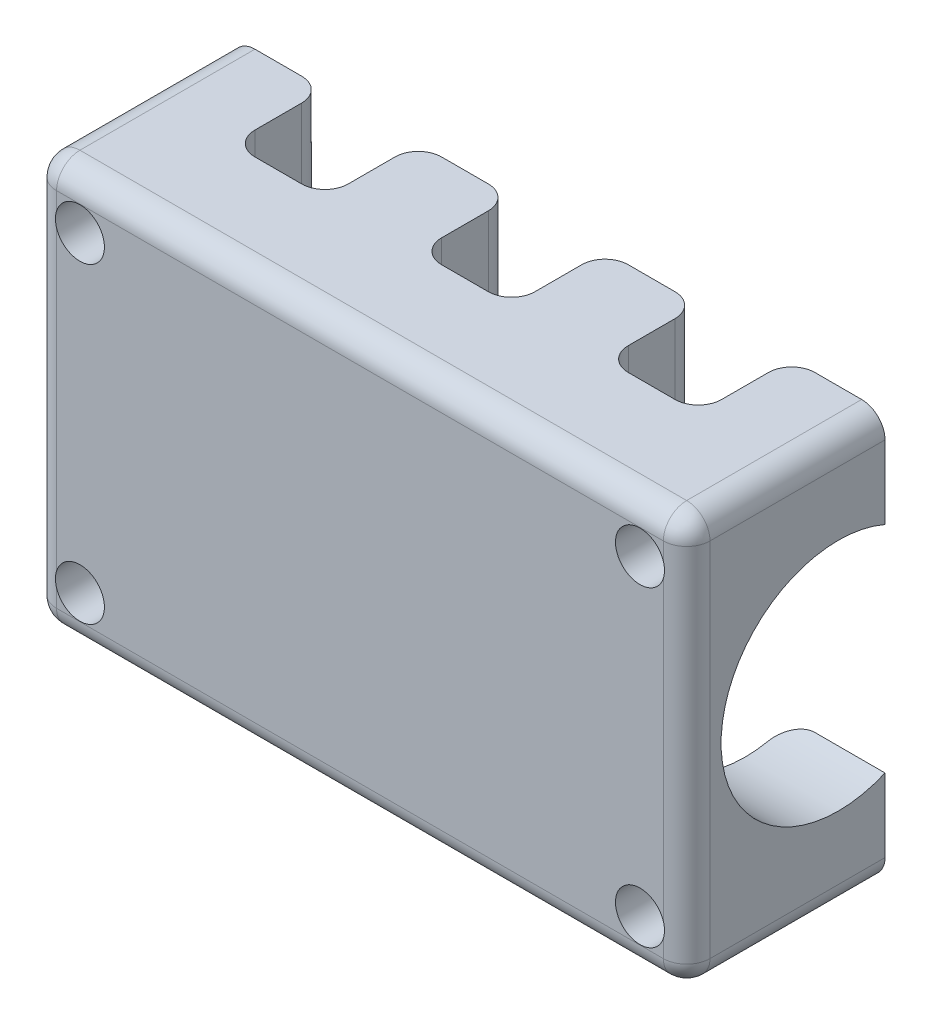
SolidWorks part; units mm, degrees
ref_plane "前视基准面" through (0, 0, 0) normal (0, 0, 1) x (1, 0, 0)
ref_plane "上视基准面" through (0, 0, 0) normal (0, 1, 0) x (1, 0, 0)
ref_plane "右视基准面" through (0, 0, 0) normal (1, 0, 0) x (0, 0, -1)
other "Configuration Table"
sketch "草图1" plane through (0, 0, 0) normal (0, 0, 1) x (1, 0, 0)
  line L1 (0, 0) -> (56, 0)
  line L2 (0, 0) -> (0, -35)
  line L3 (0, -35) -> (56, -35)
  line L4 (56, 0) -> (56, -35)
  dimension "D1" = 56
  dimension "D2" = 35
extrude "凸台-拉伸1" add sketch "草图1" along normal blind 26 contours L2 L1 L4 L3
sketch "草图2" plane through (0, 0, 0) normal (-1, 0, 0) x (0, 0, 1)
  line L0 (13, 0) -> (13, -35) construction
  line L1 (26, 0) -> (0, 0) construction
  line L2 (26, -35) -> (0, -35) construction
  line L3 (0, -17.5) -> (26, -17.5) construction
  line L4 (0, 0) -> (0, -35) construction
  line L5 (26, 0) -> (26, -35) construction
  circle A0 centre (13, -17.5) radius 10.05
  dimension "D1" = 20.1
extrude "切除-拉伸1" cut sketch "草图2" against normal blind 63
sketch "草图3" plane through (0, 0, 0) normal (0, 1, 0) x (1, 0, 0)
  line L0 (0, -13) -> (56, -13) construction
  line L3 (0, -26) -> (0, 0) construction
  line L4 (28, 0) -> (28, -26) construction
  line L5 (0, 0) -> (56, 0) construction
  line L6 (0, -26) -> (56, -26) construction
  line L15 (56, -26) -> (56, 0) construction
  line L16 (0, -9) -> (8, -9)
  line L17 (8, -9) -> (8, -17)
  line L18 (8, -17) -> (16, -17)
  line L19 (16, -17) -> (16, -9)
  line L20 (56, 0) -> (0, 0)
  line L21 (0, 0) -> (0, -26)
  line L22 (0, -26) -> (56, -26)
  line L23 (56, -26) -> (56, 0)
  line L24 (56, 0) -> (0, 0)
  line L25 (0, 0) -> (0, -26)
  line L26 (0, -26) -> (56, -26)
  line L27 (56, -26) -> (56, 0)
  line L28 (16, -9) -> (24, -9)
  line L29 (24, -9) -> (24, -17)
  line L30 (24, -17) -> (32, -17)
  line L31 (32, -17) -> (32, -9)
  line L32 (32, -9) -> (40, -9)
  line L33 (40, -9) -> (40, -17)
  line L34 (40, -17) -> (48, -17)
  line L35 (48, -17) -> (48, -9)
  line L36 (48, -9) -> (56, -9)
  line M16 (56, 0) -> (0, 0)
  line M17 (0, 0) -> (0, -26)
  dimension "D1" = 0
  dimension "D2" = 9
  dimension "D3" = 8
  dimension "D4" = 8
  dimension "D5" = 8
extrude "切除-拉伸4" cut sketch "草图3" against normal blind 41 contours L35 L36 L27 L16 L17 L18 L19 L28 L29 L30 L31 L32 L33 L34 M16 M17 region at (28, 0, 6.8448)
sketch "草图6" plane through (0, 0, 26) normal (0, 0, 1) x (1, 0, 0)
  line L0 (48, -8.2803) -> (48, 0) construction
  line L1 (48, 0) -> (56, 0) construction
  line L2 (56, 0) -> (56, -8.2803) construction
  line L3 (56, -8.2803) -> (48, -8.2803) construction
  line L4 (0, -8.2803) -> (0, 0) construction
  line L5 (0, 0) -> (8, 0) construction
  line L6 (8, 0) -> (8, -8.2803) construction
  line L7 (8, -8.2803) -> (0, -8.2803) construction
  line L8 (48, -8.2803) -> (48, 0)
  line L9 (48, 0) -> (56, 0)
  line L10 (56, 0) -> (56, -8.2803)
  line L11 (56, -8.2803) -> (48, -8.2803)
  line L12 (0, -8.2803) -> (0, 0)
  line L13 (0, 0) -> (8, 0)
  line L14 (8, 0) -> (8, -8.2803)
  line L15 (8, -8.2803) -> (0, -8.2803)
  line L16 (0, -17.5) -> (56, -17.5) construction
  line L17 (0, 0) -> (0, -35) construction
  line L18 (56, 0) -> (56, -35) construction
  line L19 (0, -4.1402) -> (56, -4.1402) construction
  line L20 (4, 0) -> (4, -8.2803) construction
  line L21 (52, 0) -> (52, -8.2803) construction
  circle A0 centre (4, -4.1402) radius 2.1
  circle A1 centre (52, -4.1402) radius 2.1
  circle A2 centre (52, -30.8598) radius 2.1
  circle A3 centre (4, -30.8598) radius 2.1
  dimension "D1" = 4.2
extrude "切除-拉伸5" cut sketch "草图6" against normal blind 41 contours A0 | A1 | A2 | A3
fillet "圆角2" radius 2 24 edges at (8, -30.8598, 9) (8, -30.8598, 17) (16, -30.8598, 17) (16, -30.8598, 9) (24, -30.8598, 9) (24, -30.8598, 17) (32, -30.8598, 17) (32, -30.8598, 9) (40, -30.8598, 9) (40, -30.8598, 17) (48, -30.8598, 17) (48, -30.8598, 9) (48, -4.1402, 9) (48, -4.1402, 17) (40, -4.1402, 17) (40, -4.1402, 9) (32, -4.1402, 9) (32, -4.1402, 17) (24, -4.1402, 17) (24, -4.1402, 9) (16, -4.1402, 9) (16, -4.1402, 17) (8, -4.1402, 17) (8, -4.1402, 9)
sketch "草图7" plane through (0, 0, 26) normal (0, 0, 1) x (1, 0, 0)
  line L0 (28, 0) -> (28, -35) construction
  line L1 (7, 0) -> (7, -35) construction
  line L2 (49, 0) -> (49, -35) construction
  line L3 (7, -25.5) -> (49, -25.5)
  line L4 (0, -35) -> (56, -35)
  line L5 (56, -35) -> (56, 0)
  line L6 (56, 0) -> (0, 0)
  line L7 (0, 0) -> (0, -35)
  line L8 (0, -35) -> (56, -35)
  line L9 (56, -35) -> (56, 0)
  line L10 (56, 0) -> (0, 0)
  line L11 (0, 0) -> (0, -35)
  line L12 (7, -25.5) -> (7, -28.5)
  line L13 (7, -28.5) -> (49, -28.5)
  line L14 (49, -28.5) -> (49, -25.5)
  dimension "D2" = 42
  dimension "D3" = 25.5
  dimension "D4" = 3
  dimension "D1" = 0
sketch "草图8" plane through (0, 0, 26) normal (0, 0, 1) x (1, 0, 0)
  line L0 (28, 0) -> (28, -35) construction
  line L1 (49, 0) -> (49, -35)
  line L2 (7, 0) -> (7, -35)
  line L3 (49, -9) -> (53, -9)
  line L4 (0, -35) -> (56, -35)
  line L5 (56, -35) -> (56, 0)
  line L6 (56, 0) -> (0, 0)
  line L7 (0, 0) -> (0, -35)
  line L8 (0, -35) -> (56, -35)
  line L9 (56, -35) -> (56, 0)
  line L10 (56, 0) -> (0, 0)
  line L11 (0, 0) -> (0, -35)
  line L12 (49, -25.5) -> (7, -25.5)
  line L13 (49, -28.5) -> (49, -25.5)
  line L14 (7, -28.5) -> (49, -28.5)
  line L15 (7, -25.5) -> (7, -28.5)
  line L16 (49, -25.5) -> (7, -25.5)
  line L17 (49, -28.5) -> (49, -25.5)
  line L18 (7, -28.5) -> (49, -28.5)
  line L19 (7, -25.5) -> (7, -28.5)
  line L20 (53, -9) -> (53, -14)
  line L21 (53, -14) -> (49, -14)
  line L22 (3, -14) -> (7, -14)
  line L23 (3, -9) -> (3, -14)
  line L24 (7, -9) -> (3, -9)
  dimension "D3" = 42
  dimension "D4" = 9
  dimension "D5" = 5
  dimension "D6" = 4
  dimension "D1" = 0
  dimension "D2" = 0
fillet "圆角3" radius 2 8 edges at (0, -35, 17.5) (56, -35, 17.5) (56, 0, 17.5) (0, 0, 17.5) (28, -35, 26) (56, -17.5, 26) (0, -17.5, 26) (28, 0, 26)
